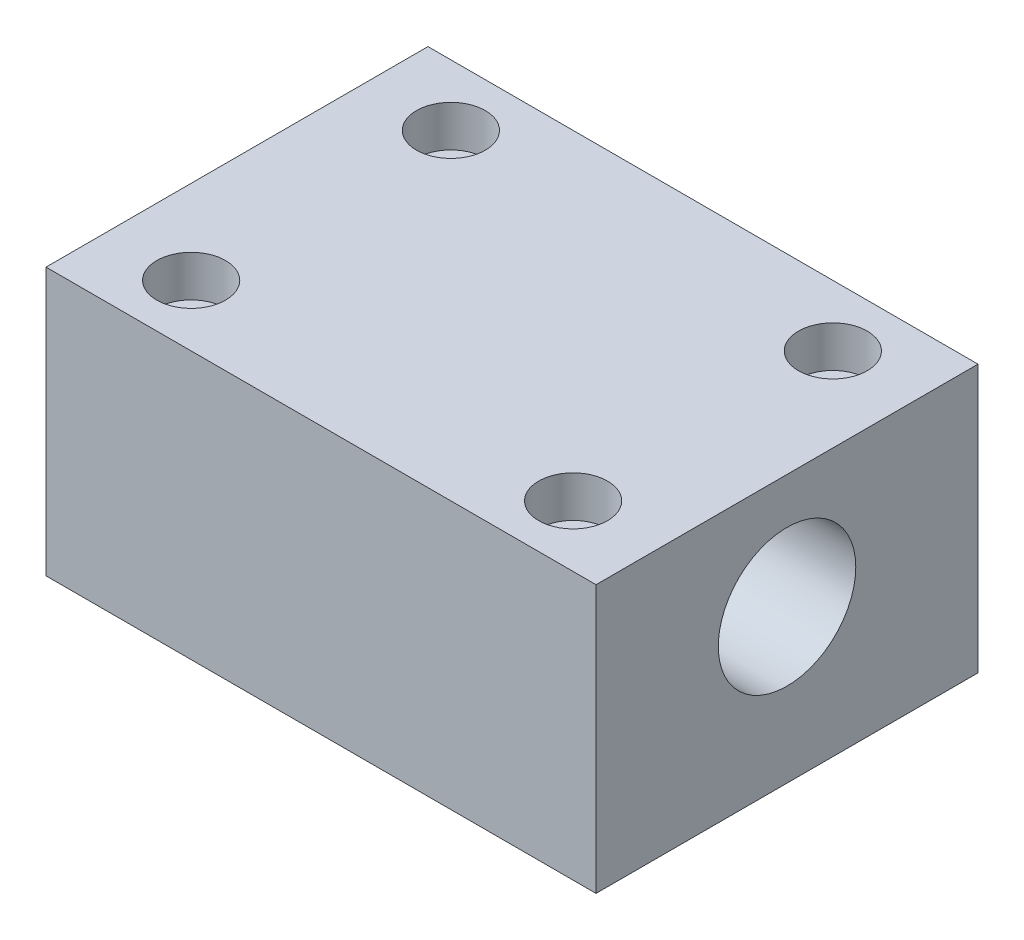
SolidWorks part; units mm, degrees
material "6061-T6 (SS)"
ref_plane "Front Plane" through (0, 0, 0) normal (0, 0, 1) x (1, 0, 0)
ref_plane "Top Plane" through (0, 0, 0) normal (0, 1, 0) x (1, 0, 0)
ref_plane "Right Plane" through (0, 0, 0) normal (1, 0, 0) x (0, 0, -1)
other "Configuration Table"
sketch "Sketch_Housing_Profile" plane through (0, 0, 0) normal (1, 0, 0) x (0, 0, -1)
  line L1 (-25, -20) -> (25, -20)
  line L2 (-25, -20) -> (-25, 15)
  line L3 (-25, 15) -> (25, 15)
  line L4 (25, -20) -> (25, 15)
extrude "Housing_Block_72x50x35" add sketch "Sketch_Housing_Profile" along normal blind 72
sketch "Sketch_Web_Clearance_Hole_9" plane through (0, 0, 0) normal (1, 0, 0) x (0, 0, -1)
  circle A0 centre (0, 0) radius 4.5
extrude "Web_Clearance_Hole_9" cut sketch "Sketch_Web_Clearance_Hole_9" along normal blind 3
ref_plane "Plane_Rear_Bushing_Seat_x3" through (3, 0, 0) normal (1, 0, 0) x (0, 0, -1)
ref_plane "Plane_Spring_Seat_x15" through (15, 0, 0) normal (1, 0, 0) x (0, 0, -1)
ref_plane "Plane_Front_Bushing_Seat_x55" through (55, 0, 0) normal (1, 0, 0) x (0, 0, -1)
sketch "Sketch_Rear_Bushing_Bore_12" plane through (3, 0, 0) normal (1, 0, 0) x (0, 0, -1)
  circle A0 centre (0, 0) radius 6
extrude "Rear_Bushing_Bore_12_H7" cut sketch "Sketch_Rear_Bushing_Bore_12" along normal blind 12
sketch "Sketch_Spring_Bore_13" plane through (15, 0, 0) normal (1, 0, 0) x (0, 0, -1)
  circle A0 centre (0, 0) radius 6.5
extrude "Spring_Pocket_Bore_13" cut sketch "Sketch_Spring_Bore_13" along normal blind 40
sketch "Sketch_Front_Bushing_Bore_18" plane through (55, 0, 0) normal (1, 0, 0) x (0, 0, -1)
  circle A0 centre (0, 0) radius 9
extrude "Front_Bushing_Bore_18_H7" cut sketch "Sketch_Front_Bushing_Bore_18" along normal blind 17
ref_plane "Plane_Housing_Top_Face_y15" through (0, 15, 0) normal (0, 1, 0) x (1, 0, 0)
sketch "Sketch_Mounting_Clearance_Holes_M5" plane through (0, 15, 0) normal (0, 1, 0) x (1, 0, 0)
  circle A0 centre (11, 17) radius 2.75
  circle A1 centre (61, 17) radius 2.75
  circle A2 centre (11, -17) radius 2.75
  circle A3 centre (61, -17) radius 2.75
extrude "Mounting_Clearance_Holes_M5" cut sketch "Sketch_Mounting_Clearance_Holes_M5" against normal blind 35
sketch "Sketch_Mounting_Counterbores_9" plane through (0, 15, 0) normal (0, 1, 0) x (1, 0, 0)
  circle A0 centre (11, 17) radius 4.5
  circle A1 centre (61, 17) radius 4.5
  circle A2 centre (11, -17) radius 4.5
  circle A3 centre (61, -17) radius 4.5
extrude "Mounting_Counterbores_9x5p4" cut sketch "Sketch_Mounting_Counterbores_9" against normal blind 5.4
ref_axis "Shaft_Axis_X" through (106.7263, 0, 0) along (-1, 0, 0)
